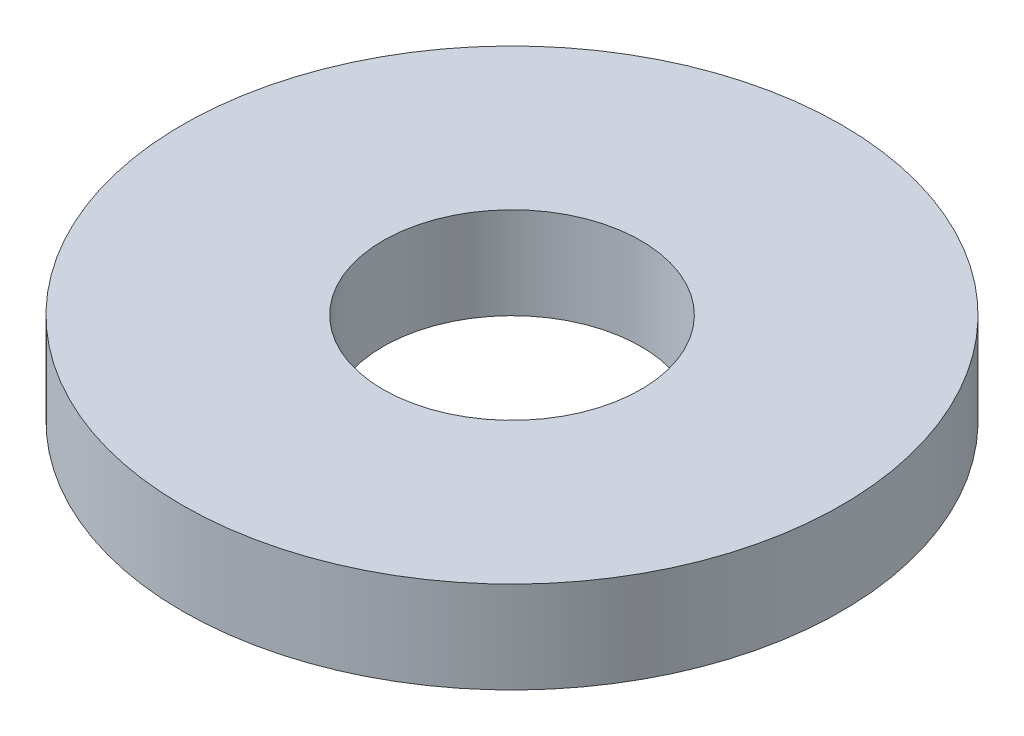
SolidWorks part; units mm, degrees
ref_plane "Front Plane" through (0, 0, 0) normal (0, 0, 1) x (1, 0, 0)
ref_plane "Top Plane" through (0, 0, 0) normal (0, 1, 0) x (1, 0, 0)
ref_plane "Right Plane" through (0, 0, 0) normal (1, 0, 0) x (0, 0, -1)
sketch "Sketch1" plane through (0, 0, 0) normal (0, 1, 0) x (1, 0, 0)
  circle A0 centre (0, 0) radius 57.5
  dimension "FLANGE_OD" = 115
extrude "Boss-Extrude1" add sketch "Sketch1" along normal blind 16
sketch "Sketch2" plane through (0, 0, 0) normal (0, 1, 0) x (1, 0, 0)
  circle A0 centre (0, 0) radius 22.5
  dimension "BORE_D" = 45
extrude "Cut-Extrude1" cut sketch "Sketch2" along normal through all
sketch "Sketch3" plane through (0, 16, 0) normal (0, 1, 0) x (1, 0, 0)
  circle A0 centre (0, 0) radius 13.1787 construction
  circle A1 centre (-13.1787, 0) radius 2.7707
  dimension "BOLT_D" = 5.5415
  dimension "BOLT_PCD" = 26.3575
extrude "Cut-Extrude2" cut sketch "Sketch3" against normal blind 11.1669 rebuild error yes
pattern_circular "CirPattern1" count 5 over 360 rebuild error yes
